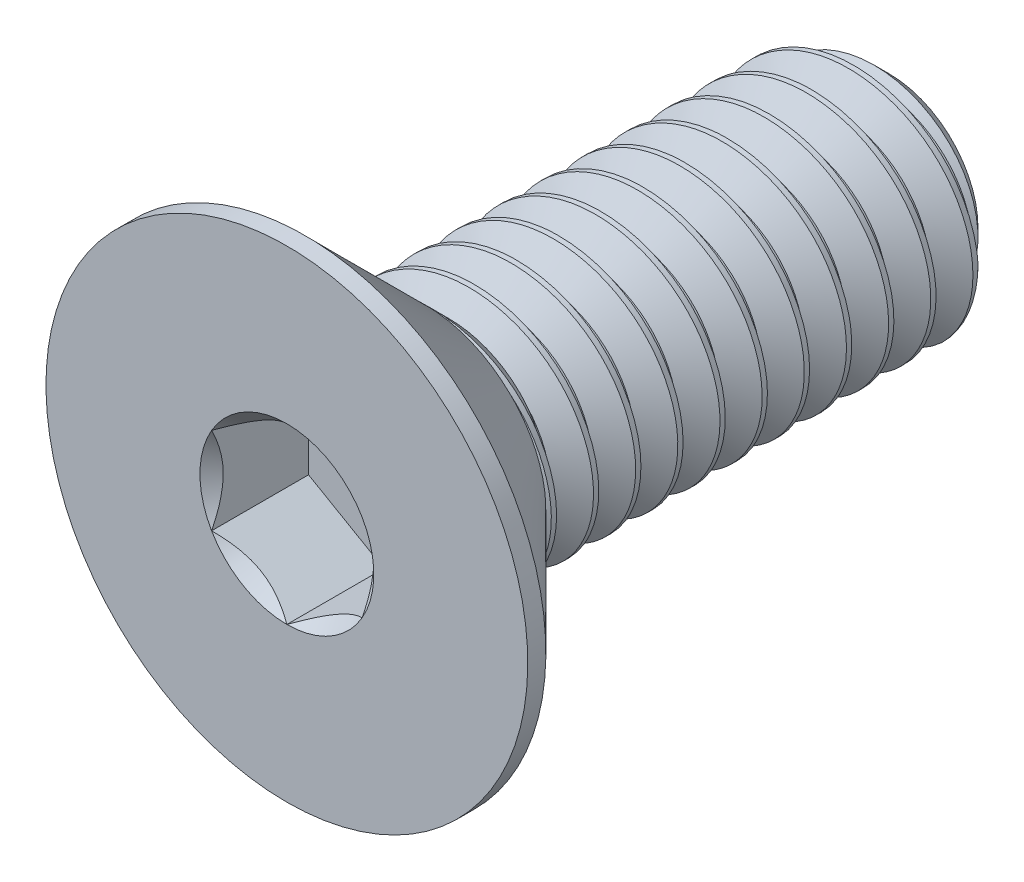
SolidWorks part; units mm, degrees
material "Alloy Steel"
ref_plane "Front" through (0, 0, 0) normal (0, 0, 1) x (1, 0, 0)
ref_plane "Top" through (0, 0, 0) normal (0, 1, 0) x (1, 0, 0)
ref_plane "Right" through (0, 0, 0) normal (1, 0, 0) x (0, 0, -1)
sketch "Sketch1" plane through (0, 0, 0) normal (1, 0, 0) x (0, 0, -1)
  line L0 (0, 4) -> (0.3, 4) construction
  line L1 (0.3, 4) -> (2.3, 2) construction
  line L2 (0, 2) -> (10, 2)
  line L3 (10, 2) -> (10, 0)
  line L4 (10, 0) -> (0, 0)
  line L5 (0, 0) -> (0, 4) construction
  line L6 (0, 4) -> (0, -4) construction
  line L7 (10, 2) -> (10, -2) construction
  line L8 (0, -4) -> (0.3, -4) construction
  line L9 (0.3, -4) -> (2.3, -2) construction
  line L11 (0, 2) -> (0, 0)
  line L12 (2.3, 2) -> (2.3, 0) construction
revolve "Revolve1" add sketch "Sketch1" angle 360 mid plane about L4
sketch "Sketch3" plane through (0, 0, -10) normal (0, 0, -1) x (-1, 0, 0)
  circle A0 centre (0, 0) radius 2
curve "Helix/Spiral1" pitch 0.7 height 10 radius 2 centre (0, 0, -10) axis (0, 0, 1) start towards (0, 1, 0)
sketch "Sketch2" plane through (0, 0, 0) normal (1, 0, 0) x (0, 0, -1)
  line L0 (10, 2) -> (10.6125, 2)
  line L1 (10.6125, 2) -> (10.35, 1.5453)
  line L2 (10.35, 1.5453) -> (10.2625, 1.5453)
  line L3 (10.2625, 1.5453) -> (10, 2)
  line L4 (10.1312, 1.7727) -> (10.4812, 1.7727) construction
  dimension "D1" = 60
  dimension "D2" = 0.0875
  dimension "D3" = 0.35
chamfer "Chamfer1" distance 0.525 angle 45 1 edges at (0, 2, -10)
sweep "Cut-Sweep1" cut profiles "Sketch2" path "Helix/Spiral1" align with end faces yes
sketch "Sketch7" plane through (0, 0, 0) normal (1, 0, 0) x (0, 0, -1)
  line L0 (0, 4) -> (0.3, 4) construction
  line L1 (0.3, 4) -> (2.3, 2) construction
  line L2 (0, 4) -> (0.3, 4)
  line L3 (0.3, 4) -> (2.3, 2)
  line L4 (2.3, 2) -> (2.3, 0) construction
  line L5 (2.3, 2) -> (2.3, 0)
  line L7 (0, 0) -> (0, 4) construction
  line L8 (0, 0) -> (0, 4)
  line L9 (0, 0) -> (2.3, 0)
  line L10 (4.4, 0) -> (-4.4, 0) construction
revolve "Revolve2" add sketch "Sketch7" angle 360 mid plane about L9
ref_plane "Plane1" through (0, 0, -2.3) normal (0, 0, 1) x (1, 0, 0)
sketch "Sketch8" plane through (0, 0, -2.3) normal (0, 0, 1) x (1, 0, 0)
  circle A0 centre (0, 0) radius 2
extrude "Boss-Extrude1" add sketch "Sketch8" against normal through all draft 45
sketch "Sketch5" plane through (0, 0, 0) normal (0, 0, 1) x (1, 0, 0)
  line L1 (1.25, -0.7217) -> (1.25, 0.7217)
  line L2 (1.25, 0.7217) -> (0, 1.4434)
  line L3 (0, 1.4434) -> (-1.25, 0.7217)
  line L4 (-1.25, 0.7217) -> (-1.25, -0.7217)
  line L5 (-1.25, -0.7217) -> (0, -1.4434)
  line L6 (0, -1.4434) -> (1.25, -0.7217)
  circle A0 centre (0, 0) radius 1.25 construction
  dimension "Hex" = 2.5
extrude "Cut-Extrude2" cut sketch "Sketch5" against normal blind 1.61
sketch "Sketch6" plane through (0, 0, 0) normal (0, 0, 1) x (1, 0, 0)
  circle A0 centre (0, 0) radius 1.4434
extrude "Cut-Extrude3" cut sketch "Sketch6" against normal blind 1.61 draft 45
sketch "Sketch9" [suppressed] plane through (0, 0, -4.4) normal (0, 0, 1) x (1, 0, 0)
  circle A1 centre (0, 0) radius 4
  circle A2 centre (0, 0) radius 4
  point P0 (0, 4)
  dimension "D1" = 0
extrude "Boss-Extrude2" [suppressed] add sketch "Sketch9" against normal offset from surface (0.6 mm away) 26 up to face at (0, 1.475, -10)
fillet "Fillet1" [suppressed] radius 0.4
sketch "Sketch10" plane through (0, 0, 0) normal (1, 0, 0) x (0, 0, -1)
  line L0 (10, 2) -> (10, -2) construction
  point P0 (8.95, -2)
  dimension "D1" = 1.05
equation "\"D3@Helix/Spiral1\" = \"Lg@Sketch1\""
equation "\"D2@Sketch2\" = \"D4@Helix/Spiral1\" * .125"
equation "\"D3@Sketch2\" = \"D4@Helix/Spiral1\" * .5"
equation "\"D1@Chamfer1\" = \"D4@Helix/Spiral1\" * .75"
equation "\"D1@Cut-Extrude2\" = \"Head Ht@Sketch1\" * .7"
equation "\"D1@Sketch10\" = \"D4@Helix/Spiral1\" * 1.5"
equation "\"D1@Cut-Extrude3\" = \"D1@Cut-Extrude2\""
equation "\"D1@Fillet1\" = \"Dia@Sketch1\" * .1"
